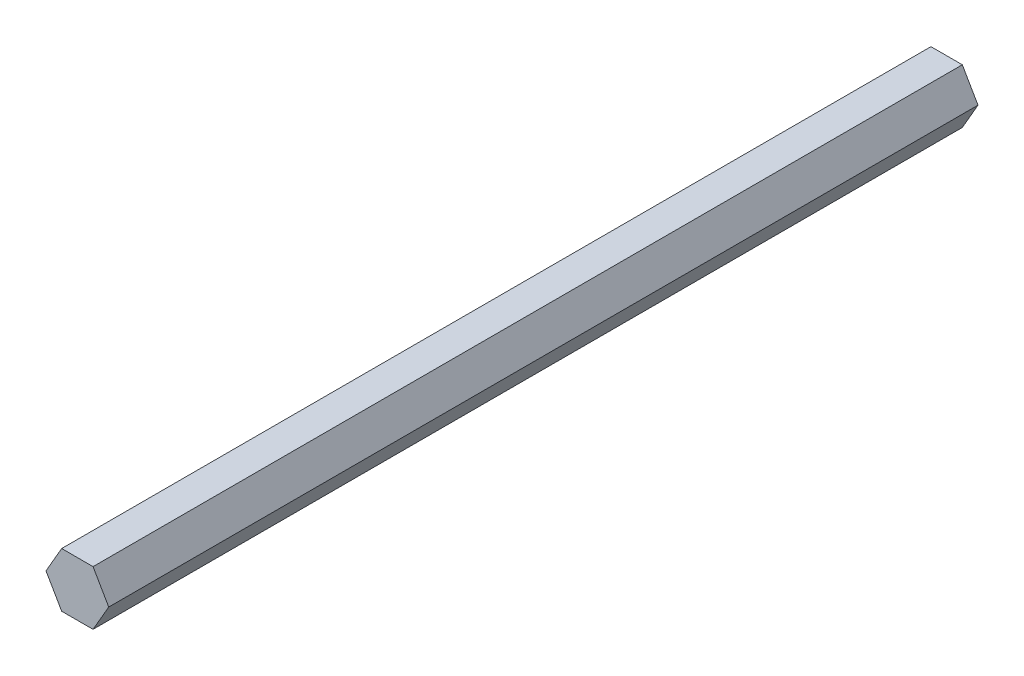
SolidWorks part; units mm, degrees
ref_plane "Front Plane" through (0, 0, 0) normal (0, 0, 1) x (1, 0, 0)
ref_plane "Top Plane" through (0, 0, 0) normal (0, 1, 0) x (1, 0, 0)
ref_plane "Right Plane" through (0, 0, 0) normal (1, 0, 0) x (0, 0, -1)
sketch "Sketch1" plane through (0, 0, 0) normal (0, 0, 1) x (1, 0, 0)
  line L1 (-7.3323, 0) -> (-3.6662, -6.35)
  line L2 (-3.6662, -6.35) -> (3.6662, -6.35)
  line L3 (3.6662, -6.35) -> (7.3323, 0)
  line L4 (7.3323, 0) -> (3.6662, 6.35)
  line L5 (3.6662, 6.35) -> (-3.6662, 6.35)
  line L6 (-3.6662, 6.35) -> (-7.3323, 0)
  circle A0 centre (0, 0) radius 6.35 construction
  dimension "D1" = 12.7
extrude "Boss-Extrude1" add sketch "Sketch1" along normal blind 203.2
ref_axis "Axis1" through (0, 0, -5.5399) along (0, 0, 1)
